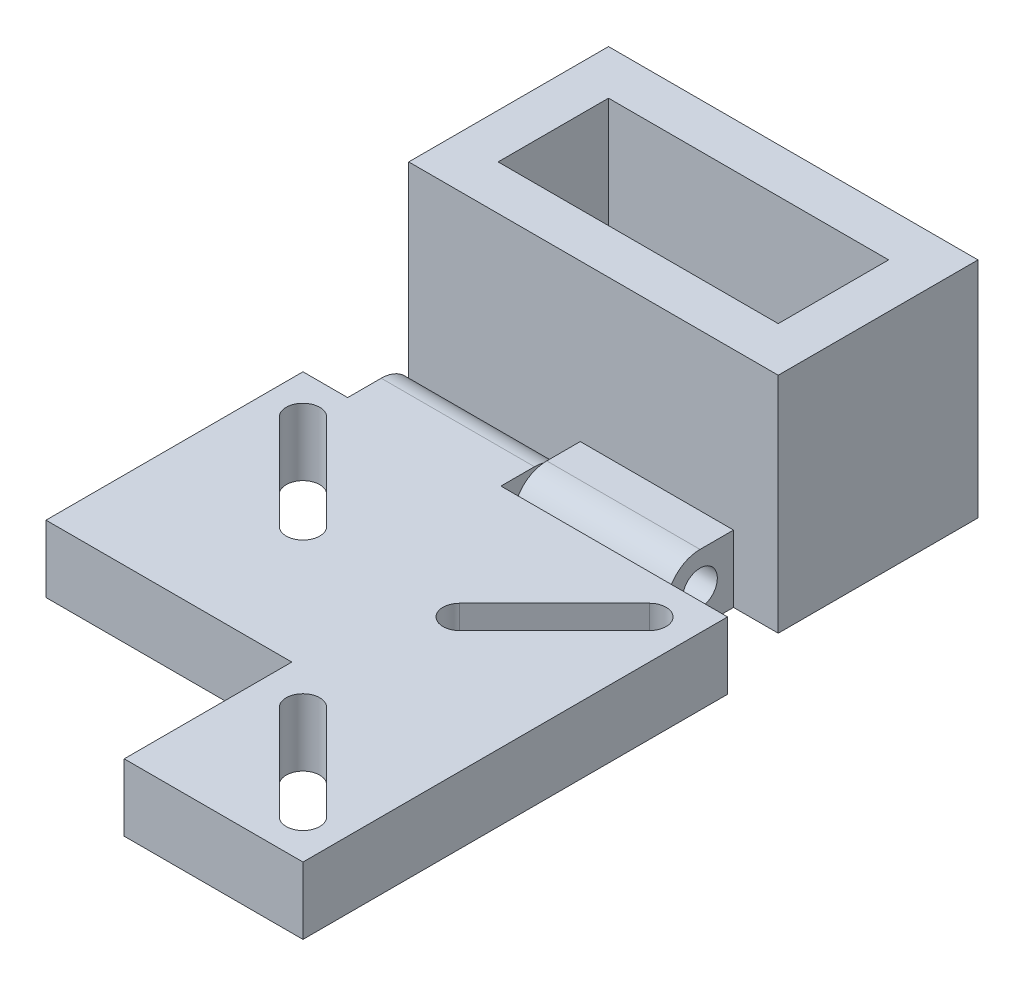
SolidWorks part; units mm, degrees
ref_plane "Front Plane" through (0, 0, 0) normal (0, 0, 1) x (1, 0, 0)
ref_plane "Top Plane" through (0, 0, 0) normal (0, 1, 0) x (1, 0, 0)
ref_plane "Right Plane" through (0, 0, 0) normal (1, 0, 0) x (0, 0, -1)
sketch "Sketch1" plane through (0, 0, 0) normal (0, 1, 0) x (1, 0, 0)
  line L0 (16.535, 8.94) -> (-16.535, 8.94)
  line L1 (12.535, -4.94) -> (-12.535, -4.94)
  line L2 (12.535, -4.94) -> (12.535, 4.94)
  line L3 (12.535, 4.94) -> (-12.535, 4.94)
  line L4 (-12.535, -4.94) -> (-12.535, 4.94)
  line L5 (12.535, -4.94) -> (-12.535, 4.94) construction
  line L6 (12.535, 4.94) -> (-12.535, -4.94) construction
  line L7 (-16.535, -8.94) -> (-16.535, 8.94)
  line L8 (16.535, -8.94) -> (-16.535, -8.94)
  line L9 (16.535, -8.94) -> (16.535, 8.94)
  line L10 (-1.1825, -8.94) -> (-1.1825, -14.94)
  line L11 (-1.1825, -14.94) -> (12.535, -14.94)
  line L12 (12.535, -14.94) -> (12.535, -8.94)
  line L13 (-1.2825, -9.94) -> (-15, -9.94)
  line L14 (-15, -9.94) -> (-15, -15.94)
  line L15 (-1.2825, -15.94) -> (-1.2825, -9.94)
  line L17 (19, -53.94) -> (-19, -53.94)
  line L18 (19, -53.94) -> (19, -15.94)
  line L19 (19, -15.94) -> (-19, -15.94)
  line L20 (-19, -53.94) -> (-19, -15.94)
  line L21 (19, -53.94) -> (-19, -15.94) construction
  line L22 (19, -15.94) -> (-19, -53.94) construction
  line L23 (-19, -38.94) -> (3, -38.94)
  line L24 (-19, -38.94) -> (-19, -53.94)
  line L25 (-19, -53.94) -> (3, -53.94)
  line L26 (3, -38.94) -> (3, -53.94)
  point P0 (0, 0)
  point P16 (0, -34.94)
  point P26 (0, -34.94)
  dimension "D2" = 0.1
  dimension "D3" = 1
  dimension "D4" = 1
  dimension "D5" = 38
  dimension "D6" = 38
  dimension "D7" = 4
  dimension "D8" = 9.88
  dimension "D9" = 25.07
  dimension "D10" = 6
  dimension "D11" = 22
  dimension "D12" = 15
  dimension "D1" = 4
extrude "Boss-Extrude1" add sketch "Sketch1" along normal blind 6 contours L20 L17 L18 L19 | L19 L15 L13 L14 | L11 L12 L8 L10 | L8 L9 L0 L7 L1 L4 L3 L2 region at (16.1591, 0, 0) region at (5.6762, 0, 11.94) region at (-8.1412, 0, 12.94) region at (2.3698, 0, 31.5334)
extrude "Boss-Extrude2" add sketch "Sketch1<3>" along normal blind 20 contours L8 L9 L0 L7 L1 L4 L3 L2 region at (16.1591, 0, 0)
sketch "Sketch1<3>" plane through (0, 0, 0) normal (0, 1, 0) x (1, 0, 0) same geometry as "Sketch1"
fillet "Fillet1" radius 3 2 edges at (5.6762, 0, 14.94) (5.6762, 6, 14.94)
fillet "Fillet2" radius 3 2 edges at (-8.1412, 0, 9.94) (-8.1412, 6, 9.94)
sketch "Sketch2" plane through (12.535, 0, 0) normal (1, 0, 0) x (0, 0, -1)
  circle A0 centre (-11.94, 3) radius 1.55
  dimension "D1" = 3.1
extrude "Cut-Extrude1" cut sketch "Sketch2" against normal up to next (13.7175 mm away)
sketch "Sketch4" plane through (-15, 0, 0) normal (-1, 0, 0) x (0, 0, 1)
  circle A0 centre (12.94, 3) radius 1.55
  dimension "D1" = 3.1
extrude "Cut-Extrude2" cut sketch "Sketch4" against normal up to next (13.7175 mm away) contours A0
sketch "Sketch5" plane through (0, 0, 0) normal (0, -1, 0) x (1, 0, 0)
  line L15 (-17, 17.94) -> (17, 51.94) construction
  line L16 (-17, 51.94) -> (17, 17.94) construction
  line L17 (-15.5, 19.44) -> (-7.0147, 27.9253) construction
  line L18 (-16.5607, 20.5007) -> (-8.0754, 28.9859)
  line L19 (-14.4393, 18.3793) -> (-5.9541, 26.8646)
  line L20 (-19, 38.94) -> (-19, 15.94) construction
  line L21 (19, 53.94) -> (19, 15.94) construction
  line L22 (19, 53.94) -> (3, 53.94) construction
  line L23 (19, 15.94) -> (-1.2825, 15.94) construction
  line L25 (-15.5, 17.94) -> (-17, 17.94) construction
  line L26 (17, 17.94) -> (-15.5, 17.94) construction
  line L27 (17, 51.94) -> (17, 17.94) construction
  line L28 (-17, 17.94) -> (-17, 51.94) construction
  line L29 (-17, 51.94) -> (17, 51.94) construction
  line L33 (15.5, 50.44) -> (7.0147, 41.9547) construction
  line L34 (16.5607, 49.3793) -> (8.0754, 40.8941)
  line L35 (14.4393, 51.5007) -> (5.9541, 43.0154)
  line L36 (15.5, 19.44) -> (7.0147, 27.9253) construction
  line L37 (14.4393, 18.3793) -> (5.9541, 26.8646)
  line L38 (16.5607, 20.5007) -> (8.0754, 28.9859)
  line L75 (-15.5, 50.44) -> (-7.0147, 41.9547) construction
  line L76 (-14.4393, 51.5007) -> (-5.9541, 43.0154)
  line L77 (-16.5607, 49.3793) -> (-8.0754, 40.8941)
  line L78 (-15.5, 50.44) -> (-7.0147, 41.9547) construction
  line L79 (-14.4393, 51.5007) -> (-5.9541, 43.0154)
  line L80 (-16.5607, 49.3793) -> (-8.0754, 40.8941)
  arc A0 (-16.5607, 20.5007) -> (-14.4393, 18.3793) centre (-15.5, 19.44) ccw
  arc A1 (-5.9541, 26.8646) -> (-8.0754, 28.9859) centre (-7.0147, 27.9253) ccw
  circle A2 centre (0, 34.94) radius 8.4203 construction
  arc A5 (16.5607, 49.3793) -> (14.4393, 51.5007) centre (15.5, 50.44) ccw
  arc A6 (5.9541, 43.0154) -> (8.0754, 40.8941) centre (7.0147, 41.9547) ccw
  arc A7 (14.4393, 18.3793) -> (16.5607, 20.5007) centre (15.5, 19.44) ccw
  arc A8 (8.0754, 28.9859) -> (5.9541, 26.8646) centre (7.0147, 27.9253) ccw
  arc A37 (-14.4393, 51.5007) -> (-16.5607, 49.3793) centre (-15.5, 50.44) ccw
  arc A38 (-8.0754, 40.8941) -> (-5.9541, 43.0154) centre (-7.0147, 41.9547) ccw
  point P2 (-11.2574, 23.6826)
  point P11 (-9.3787, 41.3187)
  point P18 (10.9774, 23.9626)
  point P21 (11.2574, 46.1974)
  point P29 (-15.5, 17.94)
  point P34 (11.2574, 23.6826)
  point P39 (0, 34.94)
  point P49 (-9.3787, 41.3187)
  point P56 (-9.3787, 41.3187)
  point P63 (-9.3787, 41.3187)
  point P70 (-9.3787, 41.3187)
  point P77 (-9.3787, 41.3187)
  point P84 (-9.3787, 41.3187)
  point P91 (-9.3787, 41.3187)
  point P98 (-9.3787, 41.3187)
  point P105 (-9.3787, 41.3187)
  point P112 (-11.2574, 46.1974)
  point P119 (-11.2574, 46.1974)
  point P126 (-11.2574, 46.1974)
  point P133 (-11.2574, 46.1974)
  point P140 (-11.2574, 46.1974)
  dimension "D2" = 12
  dimension "D3" = 3
  dimension "D1" = 2
  dimension "D5" = 2
  dimension "D6" = 2
  dimension "D4" = 4
extrude "Cut-Extrude3" cut sketch "Sketch5" against normal up to next (6 mm away)
